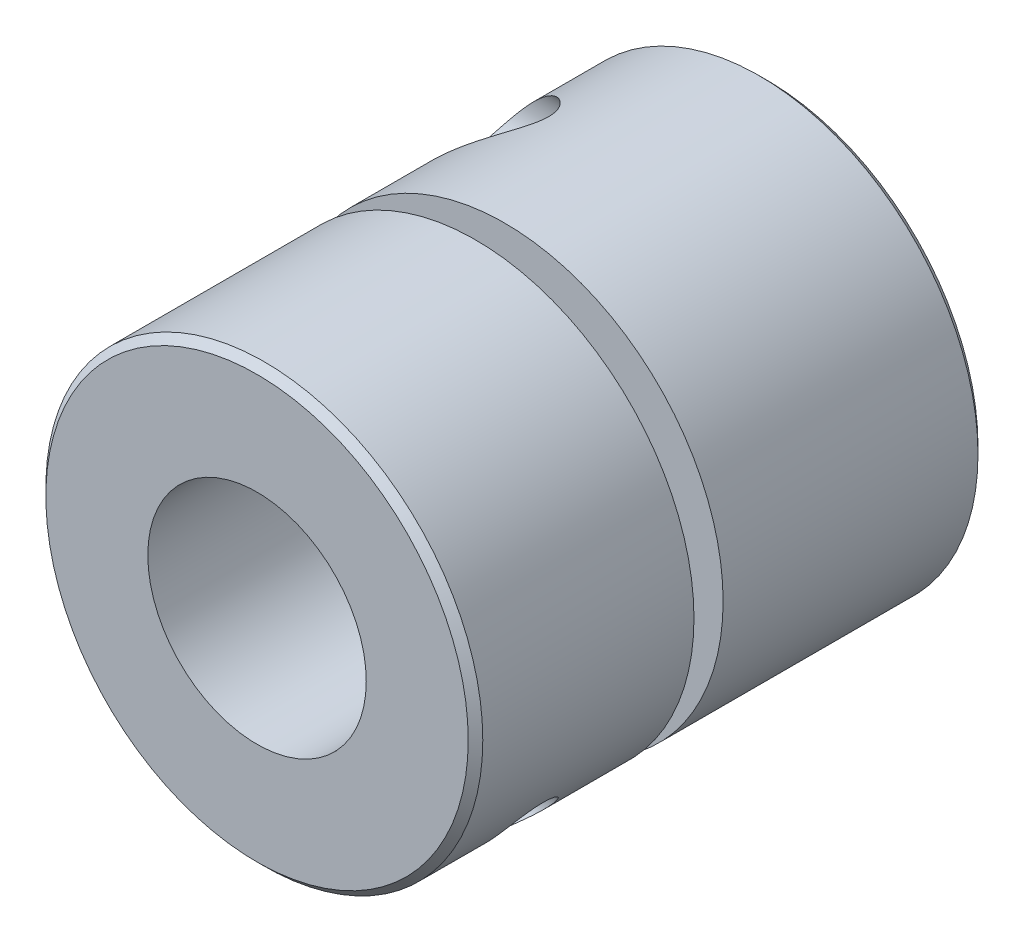
SolidWorks part; units mm, degrees
ref_plane "前视基准面" through (0, 0, 0) normal (0, 0, 1) x (1, 0, 0)
ref_plane "上视基准面" through (0, 0, 0) normal (0, 1, 0) x (1, 0, 0)
ref_plane "右视基准面" through (0, 0, 0) normal (1, 0, 0) x (0, 0, -1)
ref_axis "x轴" through (88.99, 0, 0) along (-1, 0, 0)
ref_axis "y轴" through (0, 0, -88.99) along (0, 0, 1)
ref_axis "z轴" through (0, -44, 0) along (0, 1, 0)
sketch "草图1" plane through (0, 0, 0) normal (0, 0, 1) x (1, 0, 0)
  circle A0 centre (0, 0) radius 4
  circle A1 centre (0, 0) radius 15
extrude "凸台-拉伸1" add sketch "草图1" along normal blind 35
sketch "草图2" plane through (0, 0, 35) normal (0, 0, 1) x (1, 0, 0)
  circle A0 centre (0, 0) radius 7.5
extrude "切除-拉伸1" cut sketch "草图2" against normal blind 15
sketch "草图3" plane through (0, 0, 0) normal (1, 0, 0) x (0, 0, -1)
  circle A0 centre (-8.8565, 10.1958) radius 2
extrude "切除-拉伸2" cut sketch "草图3" against normal mid plane 12
ref_plane "基准面1" through (-14, 0, 0) normal (-1, 0, 0) x (0, 0, 1)
sketch "草图4" plane through (-14, 0, 0) normal (-1, 0, 0) x (0, 0, 1)
  circle A0 centre (8.8565, 10.1958) radius 3.5
extrude "切除-拉伸3" cut sketch "草图4" against normal blind 10
ref_plane "基准面2" through (0, 0, 20) normal (0, 0, 1) x (1, 0, 0)
sketch "草图5" plane through (0, 0, 20) normal (0, 0, 1) x (1, 0, 0)
  circle A0 centre (0, 0) radius 15
  circle A1 centre (0, 0) radius 12
extrude "切除-拉伸4" cut sketch "草图5" against normal blind 2
sketch "草图6" plane through (0, 0, 0) normal (1, 0, 0) x (0, 0, -1)
  circle A0 centre (-27.8779, -10.25) radius 2
  point P2 (-27.8779, -10.25)
extrude "切除-拉伸5" cut sketch "草图6" against normal mid plane 40
chamfer "倒角1" distance 0.5 angle 45 2 edges at (15, 0, 0) (15, 0, 35)
